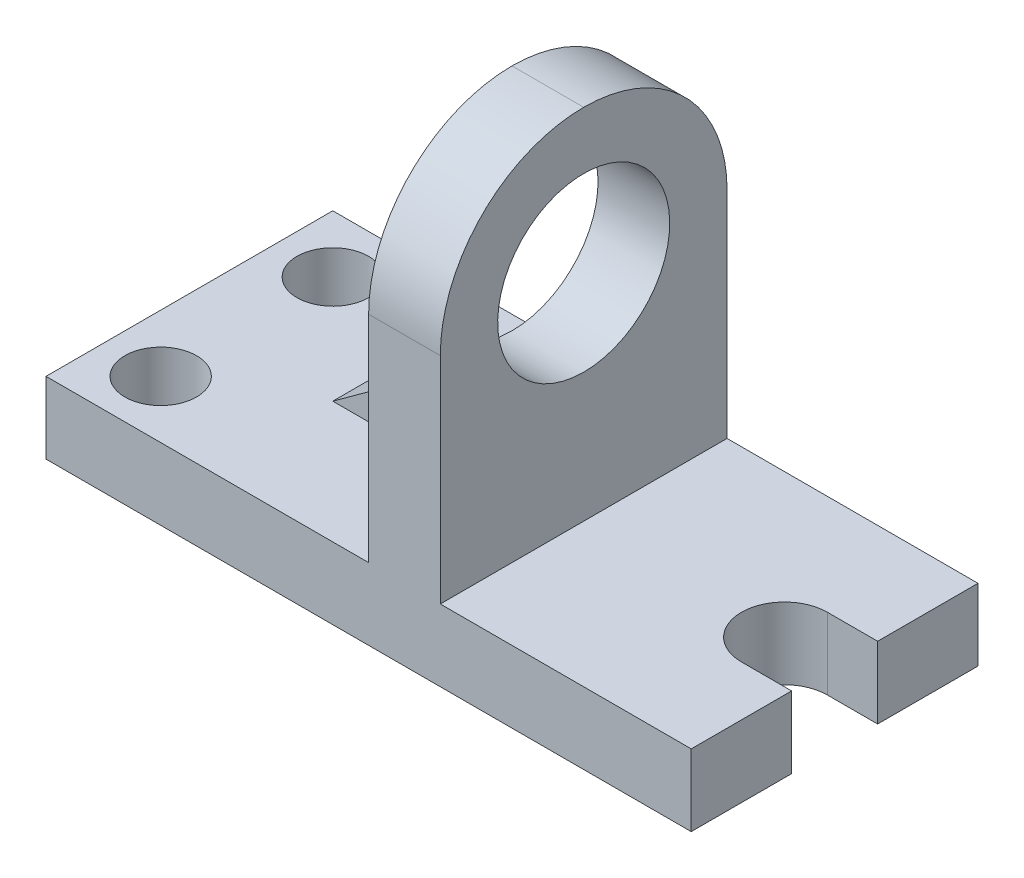
SolidWorks part; units mm, degrees
ref_plane "Спереди" through (0, 0, 0) normal (0, 0, 1) x (1, 0, 0)
ref_plane "Сверху" through (0, 0, 0) normal (0, 1, 0) x (1, 0, 0)
ref_plane "Справа" through (0, 0, 0) normal (1, 0, 0) x (0, 0, -1)
sketch "Эскиз1" plane through (0, 0, 0) normal (0, 0, 1) x (1, 0, 0)
  line L0 (-13.5, 2.5) -> (-2.5, 10.5)
  line L1 (-20, -2.5) -> (20, -2.5)
  line L2 (-20, -2.5) -> (-20, 2.5)
  line L3 (-20, 2.5) -> (20, 2.5)
  line L4 (20, -2.5) -> (20, 2.5)
  line L5 (-20, -2.5) -> (20, 2.5) construction
  line L6 (-20, 2.5) -> (20, -2.5) construction
  line L7 (-2.5, 27.5) -> (2.5, 27.5)
  line L8 (-2.5, 27.5) -> (-2.5, 2.5)
  line L9 (-2.5, 2.5) -> (2.5, 2.5)
  line L10 (2.5, 27.5) -> (2.5, 2.5)
  line L11 (-2.5, 27.5) -> (2.5, 2.5) construction
  line L12 (-2.5, 2.5) -> (2.5, 27.5) construction
  point P0 (0, 0)
  point P6 (0, 15)
  dimension "D1" = 5
  dimension "D2" = 40
  dimension "D3" = 25
  dimension "D4" = 11
  dimension "D5" = 8
extrude "Бобышка-Вытянуть1" add sketch "Эскиз1" along normal blind 10 and the other way blind 10 contours L1 L4 L3 L2 | L10 L7 L8 L3 region at (0, 0, 0) region at (0, 15, 0)
extrude "Бобышка-Вытянуть2" add sketch "Эскиз1<3>" along normal blind 1.5 and the other way blind 1.5 contours L8 L0 L3 region at (-6.1667, 5.1667, 0)
sketch "Эскиз1<3>" plane through (0, 0, 0) normal (0, 0, 1) x (1, 0, 0) same geometry as "Эскиз1"
fillet "Скругление1" radius 10 2 edges at (0, 27.5, 10) (0, 27.5, -10)
sketch "Эскиз2" plane through (-2.5, 0, 0) normal (-1, 0, 0) x (0, 0, 1)
  circle A0 centre (0, 17.5) radius 6
  dimension "D1" = 12
extrude "Вырез-Вытянуть1" cut sketch "Эскиз2" against normal through all contours A0
sketch "Эскиз4" plane through (0, 2.5, 0) normal (0, 1, 0) x (1, 0, 0)
  line L0 (16.5, 3) -> (20, 3)
  line L1 (20, 10) -> (20, -10) construction
  line L2 (20, 3) -> (20, -3)
  line L3 (20, -3) -> (16.5, -3)
  circle A0 centre (16.5, 0) radius 3
  line M3 (20, -10) -> (20, 10)
  dimension "D1" = 6
  dimension "D2" = 3.5
extrude "Вырез-Вытянуть3" cut sketch "Эскиз4" against normal through all contours A0 L3 L0 M3 | A0 region at (18.25, 2.5, -2.9305) region at (16.5, 2.5, 0)
sketch "Эскиз5" plane through (-20, 0, 0) normal (-1, 0, 0) x (0, 0, 1)
  line L4 (-10, -2.5) -> (10, -2.5)
  line L5 (10, -2.5) -> (10, 2.5)
  line L6 (10, 2.5) -> (-10, 2.5)
  line L7 (-10, 2.5) -> (-10, -2.5)
  line L8 (-10, -2.5) -> (10, -2.5)
  line L9 (10, -2.5) -> (10, 2.5)
  line L10 (10, 2.5) -> (-10, 2.5)
  line L11 (-10, 2.5) -> (-10, -2.5)
  dimension "D1" = 0
extrude "Бобышка-Вытянуть3" add sketch "Эскиз5" along normal blind 5
sketch "Эскиз3" plane through (0, 2.5, 0) normal (0, 1, 0) x (1, 0, 0)
  line L1 (-25, -10) -> (-2.5, -10) construction
  line L2 (-25, -10) -> (-25, 10) construction
  circle A0 centre (-21, -6) radius 2.5
  dimension "D1" = 5
  dimension "D3" = 4
  dimension "D2" = 4
extrude "Вырез-Вытянуть4" cut sketch "Эскиз3" against normal through all contours A0
mirror "Зеркальное отражение1" about plane through (0, 0, 0) normal (0, 0, 1) of "Вырез-Вытянуть4"
